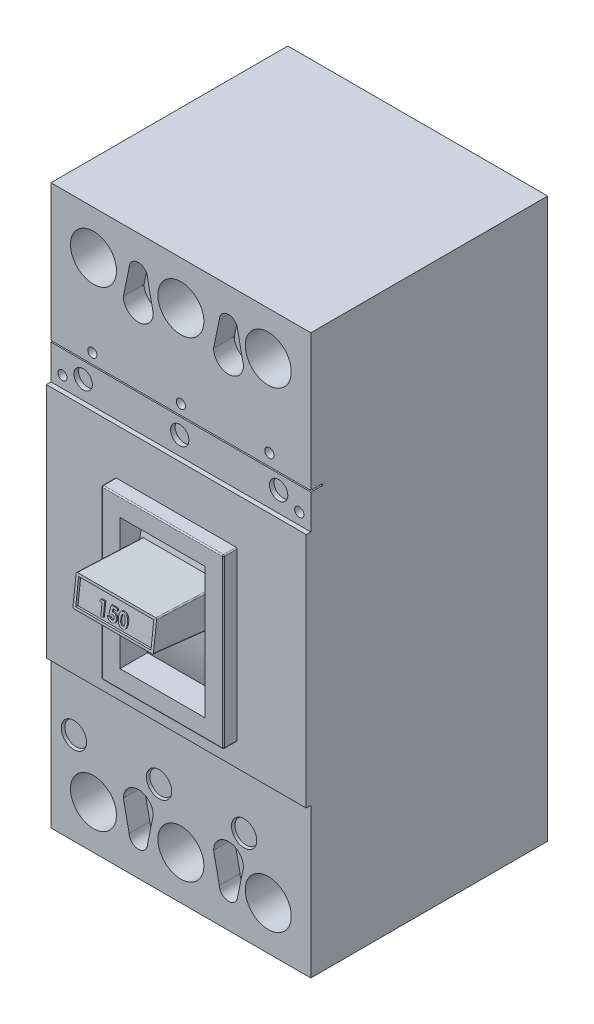
SolidWorks part; units mm, degrees
ref_plane "Alzado" through (0, 0, 0) normal (0, 0, 1) x (1, 0, 0)
ref_plane "Planta" through (0, 0, 0) normal (0, 1, 0) x (1, 0, 0)
ref_plane "Vista lateral" through (0, 0, 0) normal (1, 0, 0) x (0, 0, -1)
sketch "Croquis1" plane through (0, 0, 0) normal (0, 0, 1) x (1, 0, 0)
  line L1 (-56.5, -121.5) -> (56.5, -121.5)
  line L2 (-56.5, -121.5) -> (-56.5, 121.5)
  line L3 (-56.5, 121.5) -> (56.5, 121.5)
  line L4 (56.5, -121.5) -> (56.5, 121.5)
  line L5 (-56.5, -121.5) -> (56.5, 121.5) construction
  line L6 (-56.5, 121.5) -> (56.5, -121.5) construction
  point P0 (0, 0)
  dimension "D1" = 113
  dimension "D2" = 243
extrude "Saliente-Extruir1" add sketch "Croquis1" along normal blind 105
sketch "Croquis2" plane through (0, 0, 105) normal (0, 0, 1) x (1, 0, 0)
  line L0 (56.5, -121.5) -> (56.5, -56.5)
  line L1 (56.5, -121.5) -> (56.5, 121.5) construction
  line L2 (56.5, -56.5) -> (-56.5, -56.5)
  line L3 (-56.5, 121.5) -> (-56.5, -121.5) construction
  line L4 (-56.5, -56.5) -> (-56.5, -121.5)
  line L5 (-56.5, -121.5) -> (56.5, -121.5)
  dimension "D1" = 65
extrude "Cortar-Extruir1" cut sketch "Croquis2" against normal blind 2
sketch "Croquis3" plane through (0, 0, 105) normal (0, 0, 1) x (1, 0, 0)
  line L0 (-56.5, 121.5) -> (-56.5, 46.5)
  line L1 (-56.5, 121.5) -> (-56.5, -56.5) construction
  line L2 (-56.5, 46.5) -> (56.5, 46.5)
  line L3 (56.5, -56.5) -> (56.5, 121.5) construction
  line L4 (56.5, 46.5) -> (56.5, 121.5)
  line L5 (56.5, 121.5) -> (-56.5, 121.5)
  dimension "D1" = 75
extrude "Cortar-Extruir2" cut sketch "Croquis3" against normal blind 2
sketch "Croquis4" plane through (0, 0, 105) normal (0, 0, 1) x (1, 0, 0)
  line L0 (56.5, -56.5) -> (56.5, 46.5) construction
  line L1 (-26.5, -46.5) -> (26.5, -46.5)
  line L2 (-26.5, -46.5) -> (-26.5, 26.5)
  line L3 (-26.5, 26.5) -> (26.5, 26.5)
  line L4 (26.5, -46.5) -> (26.5, 26.5)
  line L5 (-26.5, -46.5) -> (26.5, 26.5) construction
  line L6 (-26.5, 26.5) -> (26.5, -46.5) construction
  line L7 (-56.5, 46.5) -> (56.5, 46.5) construction
  line L8 (-56.5, 46.5) -> (-56.5, -56.5) construction
  line L9 (56.5, -56.5) -> (-56.5, -56.5) construction
  point P0 (0, -10)
  dimension "D1" = 30
  dimension "D2" = 20
  dimension "D3" = 30
  dimension "D4" = 10
extrude "Saliente-Extruir2" add sketch "Croquis4" along normal blind 6
sketch "Croquis5" plane through (0, 0, 111) normal (0, 0, 1) x (1, 0, 0)
  line L0 (26.5, -46.5) -> (26.5, 26.5) construction
  line L1 (-18.5, -38.5) -> (18.5, -38.5)
  line L2 (-18.5, -38.5) -> (-18.5, 18.5)
  line L3 (-18.5, 18.5) -> (18.5, 18.5)
  line L4 (18.5, -38.5) -> (18.5, 18.5)
  line L5 (-18.5, -38.5) -> (18.5, 18.5) construction
  line L6 (-18.5, 18.5) -> (18.5, -38.5) construction
  line L7 (26.5, 26.5) -> (-26.5, 26.5) construction
  line L8 (-26.5, 26.5) -> (-26.5, -46.5) construction
  line L9 (-26.5, -46.5) -> (26.5, -46.5) construction
  point P0 (0, -10)
  point P11 (-18.5, -10)
  dimension "D1" = 8
  dimension "D2" = 8
  dimension "D3" = 8
  dimension "D4" = 8
extrude "Cortar-Extruir3" cut sketch "Croquis5" against normal blind 7
sketch "Croquis6" plane through (-18.5, 0, 0) normal (1, 0, 0) x (0, 0, -1)
  line L0 (-104, 18.5) -> (-99, 18.5)
  line L1 (-104, -38.5) -> (-99, -38.5)
  line L2 (-104, 18.5) -> (-106.9692, 18.5)
  line L3 (-106.9692, 18.5) -> (-106.9692, -38.5)
  line L4 (-106.9692, -38.5) -> (-104, -38.5)
  arc A0 (-99, -38.5) -> (-99, 18.5) centre (-20.275, -10) cw
  dimension "D1" = 5
extrude "Cortar-Extruir4" cut sketch "Croquis6" along normal up to surface (37 mm away) up to face at (18.5, -10, 107.5)
sketch "Croquis7" plane through (-18.5, 0, 0) normal (1, 0, 0) x (0, 0, -1)
  line L0 (-102.2276, 7.1359) -> (-131, 8.458)
  line L1 (-111, -46.5) -> (-111, 26.5) construction
  line L2 (-131, 8.458) -> (-132.497, -4.4555)
  line L3 (-132.497, -4.4555) -> (-103.9701, -7.7626)
  arc A0 (-99, 18.5) -> (-99, -38.5) centre (-20.275, -10) ccw construction
  arc A1 (-102.2276, 7.1359) -> (-103.9701, -7.7626) centre (-20.275, -10) ccw
  dimension "D1" = 20
  dimension "D2" = 13
  dimension "D3" = 15
extrude "Saliente-Extruir3" add sketch "Croquis7" along normal up to surface (37 mm away) up to face at (18.5, -10, 106.25)
sketch "Croquis9" plane through (18.5, 0, 0) normal (1, 0, 0) x (0, 0, -1)
  line L0 (-131, 8.458) -> (-102.2276, 7.1359)
  line L1 (-131, 8.458) -> (-132.497, -4.4555)
  line L2 (-132.497, -4.4555) -> (-103.9701, -7.7626)
  arc A0 (-103.9701, -7.7626) -> (-102.2276, 7.1359) centre (-38.2725, -7.8951) cw
extrude "Cortar-Extruir5" cut sketch "Croquis9" against normal blind 1
sketch "Croquis10" plane through (-18.5, 0, 0) normal (-1, 0, 0) x (0, 0, 1)
  line L0 (102.2276, 7.1359) -> (131, 8.458)
  line L1 (131, 8.458) -> (132.497, -4.4555)
  line L2 (132.497, -4.4555) -> (103.9701, -7.7626)
  arc A0 (103.9701, -7.7626) -> (102.2276, 7.1359) centre (38.2725, -7.8951) ccw
extrude "Cortar-Extruir6" cut sketch "Croquis10" against normal blind 1
sketch "Croquis11" plane through (0, 15.0972, 130.2303) normal (0, 0.1152, 0.9933) x (1, 0, 0)
  line L1 (-16.3625, -18.6242) -> (16.3625, -18.6242)
  line L2 (-16.3625, -18.6242) -> (-16.3625, -7.7431)
  line L3 (-16.3625, -7.7431) -> (16.3625, -7.7431)
  line L4 (16.3625, -18.6242) -> (16.3625, -7.7431)
  line L5 (-16.3625, -18.6242) -> (16.3625, -7.7431) construction
  line L6 (-16.3625, -7.7431) -> (16.3625, -18.6242) construction
  point P0 (0, -13.1836)
extrude "Cortar-Extruir7" cut sketch "Croquis11" against normal blind 1
fillet "Redondeo1" radius 0.5 4 edges at (17.5, -6.109, 118.2336) (17.5, 7.7969, 116.6138) (-17.5, -6.109, 118.2336) (-17.5, 7.7969, 116.6138)
sketch "Croquis12" plane through (0, 14.982, 129.237) normal (0, 0.1152, 0.9933) x (1, 0, 0)
  line L0 (-10.1967, -17.2783) -> (10.7691, -17.2783) construction
  text T0 " 150" font "Century Gothic" height in points 22
extrude "Saliente-Extruir4" add sketch "Croquis12" along normal blind 0.5
fillet "Redondeo2" radius 0.5 8 edges at (-26.5, -46.5, 108) (26.5, -46.5, 108) (0, -46.5, 111) (26.5, -10, 111) (26.5, 26.5, 108) (0, 26.5, 111) (-26.5, -10, 111) (-26.5, 26.5, 108)
sketch "Croquis13" plane through (0, 0, 103) normal (0, 0, 1) x (1, 0, 0)
  line L0 (56.5, 121.5) -> (-56.5, 121.5) construction
  line L1 (56.5, 121.5) -> (56.5, -121.5) construction
  line L2 (56.5, 0) -> (-56.5, 0) construction
  line L3 (-56.5, 46.5) -> (-56.5, -56.5) construction
  circle A0 centre (0, 102.5) radius 10
  circle A1 centre (-38, 102.5) radius 10
  circle A2 centre (38, 102.5) radius 10
  circle A3 centre (38, -102.5) radius 10
  circle A4 centre (-38, -102.5) radius 10
  circle A5 centre (0, -102.5) radius 10
  dimension "D1" = 20
  dimension "D3" = 38
  dimension "D4" = 20
  dimension "D7" = 38
  dimension "D8" = 20
  dimension "D2" = 19
  dimension "D5" = 19
  dimension "D6" = 19
extrude "Cortar-Extruir8" cut sketch "Croquis13" against normal blind 39
sketch "Croquis14" plane through (0, 0, 103) normal (0, 0, 1) x (1, 0, 0)
  line L0 (-56.5, 46.5) -> (56.5, 46.5) construction
  line L1 (-56.5, 121.5) -> (-56.5, 46.5) construction
  line L2 (-25, 94.5) -> (-22.5, 106.5)
  line L3 (-12, 94.5) -> (-14.5, 106.5)
  line L4 (14.2234, 94.5) -> (16.7234, 106.5)
  line L5 (24.7234, 106.5) -> (27.2234, 94.5)
  line L6 (56.5, 121.5) -> (56.5, -121.5) construction
  line L7 (56.5, 0) -> (-56.5, 0) construction
  line L8 (-56.5, 46.5) -> (-56.5, -56.5) construction
  line L9 (24.7234, -106.5) -> (27.2234, -94.5)
  line L10 (14.2234, -94.5) -> (16.7234, -106.5)
  line L11 (-12, -94.5) -> (-14.5, -106.5)
  line L12 (-25, -94.5) -> (-22.5, -106.5)
  arc A0 (-25, 94.5) -> (-12, 94.5) centre (-18.5, 94.5) ccw
  arc A1 (14.2234, 94.5) -> (27.2234, 94.5) centre (20.7234, 94.5) ccw
  arc A2 (-14.5, 106.5) -> (-22.5, 106.5) centre (-18.5, 106.5) ccw
  arc A3 (24.7234, 106.5) -> (16.7234, 106.5) centre (20.7234, 106.5) ccw
  arc A4 (24.7234, -106.5) -> (16.7234, -106.5) centre (20.7234, -106.5) cw
  arc A5 (-14.5, -106.5) -> (-22.5, -106.5) centre (-18.5, -106.5) cw
  arc A6 (14.2234, -94.5) -> (27.2234, -94.5) centre (20.7234, -94.5) cw
  arc A7 (-25, -94.5) -> (-12, -94.5) centre (-18.5, -94.5) cw
  dimension "D3" = 48
  dimension "D4" = 13
  dimension "D5" = 13
  dimension "D8" = 8
  dimension "D9" = 8
  dimension "D1" = 48
  dimension "D2" = 38
  dimension "D6" = 12
  dimension "D7" = 12
extrude "Cortar-Extruir9" cut sketch "Croquis14" against normal blind 9
sketch "Croquis15" plane through (0, 0, 94) normal (0, 0, 1) x (1, 0, 0)
  circle A0 centre (-18.5, 94.5) radius 3.5
  circle A1 centre (20.7234, 94.5) radius 3.5
  circle A2 centre (-18.5, 106.5) radius 2.5
  circle A3 centre (20.7234, 106.5) radius 2.5
  dimension "D1" = 7
  dimension "D2" = 7
  dimension "D3" = 5
  dimension "D4" = 5
extrude "Cortar-Extruir10" cut sketch "Croquis15" against normal up to surface (94 mm away) up to face at (0, 0, 0)
sketch "Croquis16" plane through (0, 0, 94) normal (0, 0, 1) x (1, 0, 0)
  circle A0 centre (-18.5, -94.5) radius 3.5
  circle A1 centre (-18.5, -106.5) radius 2.5
  circle A4 centre (20.7234, -94.5) radius 3.5
  circle A5 centre (20.7234, -106.5) radius 2.5
  dimension "D1" = 7
  dimension "D2" = 5
  dimension "D3" = 7
  dimension "D4" = 5
extrude "Cortar-Extruir11" cut sketch "Croquis16" against normal up to surface (94 mm away) up to face at (17.2234, 94.5, 0)
sketch "Croquis17" plane through (0, 0, 103) normal (0, 0, 1) x (1, 0, 0)
  line L0 (-56.5, 121.5) -> (-56.5, 46.5) construction
  line L1 (-56.5, 46.5) -> (56.5, 46.5) construction
  line L2 (56.5, 46.5) -> (56.5, 121.5) construction
  circle A0 centre (-42.5, 54.5) radius 4
  circle A1 centre (-0.5, 54.5) radius 4
  circle A2 centre (42.5, 55.2532) radius 4
  dimension "D1" = 8
  dimension "D4" = 8
  dimension "D6" = 42
  dimension "D7" = 8
  dimension "D2" = 14
  dimension "D3" = 8
  dimension "D5" = 8
  dimension "D8" = 14
extrude "Cortar-Extruir12" cut sketch "Croquis17" against normal blind 2
sketch "Croquis18" plane through (0, 0, 103) normal (0, 0, 1) x (1, 0, 0)
  line L0 (-56.5, 46.5) -> (56.5, 46.5) construction
  line L1 (-56.5, 121.5) -> (-56.5, 46.5) construction
  line L2 (56.5, 46.5) -> (56.5, 121.5) construction
  circle A0 centre (-51.5, 51.5) radius 2
  circle A1 centre (51.5, 51.5) radius 2
  circle A2 centre (0, 66.5) radius 2
  circle A3 centre (38.5, 67.2532) radius 2
  circle A4 centre (-38.5, 66.5) radius 2
  circle A5 centre (-0.5, 54.5) radius 4 construction
  circle A6 centre (42.5, 55.2532) radius 4 construction
  circle A7 centre (-42.5, 54.5) radius 4 construction
  dimension "D1" = 4
  dimension "D2" = 4
  dimension "D4" = 5
  dimension "D7" = 4
  dimension "D8" = 4
  dimension "D9" = 4
  dimension "D10" = 12
  dimension "D11" = 12
  dimension "D13" = 12
  dimension "D14" = 18
  dimension "D3" = 5
  dimension "D5" = 5
  dimension "D6" = 5
  dimension "D12" = 18
extrude "Cortar-Extruir13" cut sketch "Croquis18" against normal blind 10
sketch "Croquis19" plane through (0, 0, 103) normal (0, 0, 1) x (1, 0, 0)
  line L0 (-56.5, 61.5) -> (56.5, 61.5)
  line L1 (-56.5, 121.5) -> (-56.5, 46.5) construction
  line L2 (56.5, 46.5) -> (56.5, 121.5) construction
  line L3 (56.5, 61.5) -> (56.5, 62.1)
  line L4 (56.5, 62.1) -> (-56.5, 62.1)
  line L5 (-56.5, 62.1) -> (-56.5, 61.5)
  dimension "D1" = 15
  dimension "D2" = 0.6
extrude "Cortar-Extruir14" cut sketch "Croquis19" against normal blind 5
sketch "Croquis20" plane through (0, 0, 103) normal (0, 0, 1) x (1, 0, 0)
  line L0 (-56.5, -56.5) -> (-56.5, -121.5) construction
  circle A0 centre (-9.5, -81.5) radius 5.5
  circle A1 centre (27.5, -81.5) radius 5.5
  circle A2 centre (-46.5, -81.5) radius 5.5
  circle A3 centre (-38, -102.5) radius 10 construction
  circle A4 centre (0, -102.5) radius 10 construction
  circle A5 centre (38, -102.5) radius 10 construction
  dimension "D1" = 11
  dimension "D3" = 21
  dimension "D4" = 11
  dimension "D5" = 37
  dimension "D6" = 21
  dimension "D7" = 11
  dimension "D8" = 37
  dimension "D9" = 21
  dimension "D2" = 10
extrude "Cortar-Extruir15" cut sketch "Croquis20" against normal blind 5
sketch "Croquis21" plane through (0, 0, 98) normal (0, 0, 1) x (1, 0, 0)
  circle A0 centre (-46.5, -81.5) radius 5
  circle A1 centre (-9.5, -81.5) radius 5
  circle A2 centre (27.5, -81.5) radius 5
  dimension "D1" = 10
  dimension "D2" = 10
  dimension "D3" = 10
extrude "Saliente-Extruir5" add sketch "Croquis21" along normal blind 4
sketch "Croquis22" plane through (0, 0, 102) normal (0, 0, 1) x (1, 0, 0)
  line L0 (-49.4105, -77.4344) -> (-43.5895, -85.5656) construction
  line L1 (-12.4105, -77.4344) -> (-6.5895, -85.5656) construction
  line L2 (24.5895, -77.4344) -> (30.4105, -85.5656) construction
  circle A0 centre (-46.5, -81.5) radius 5 construction
  circle A1 centre (-9.5, -81.5) radius 5 construction
  circle A2 centre (27.5, -81.5) radius 5 construction
  circle A3 centre (27.5, -81.5) radius 5 construction
